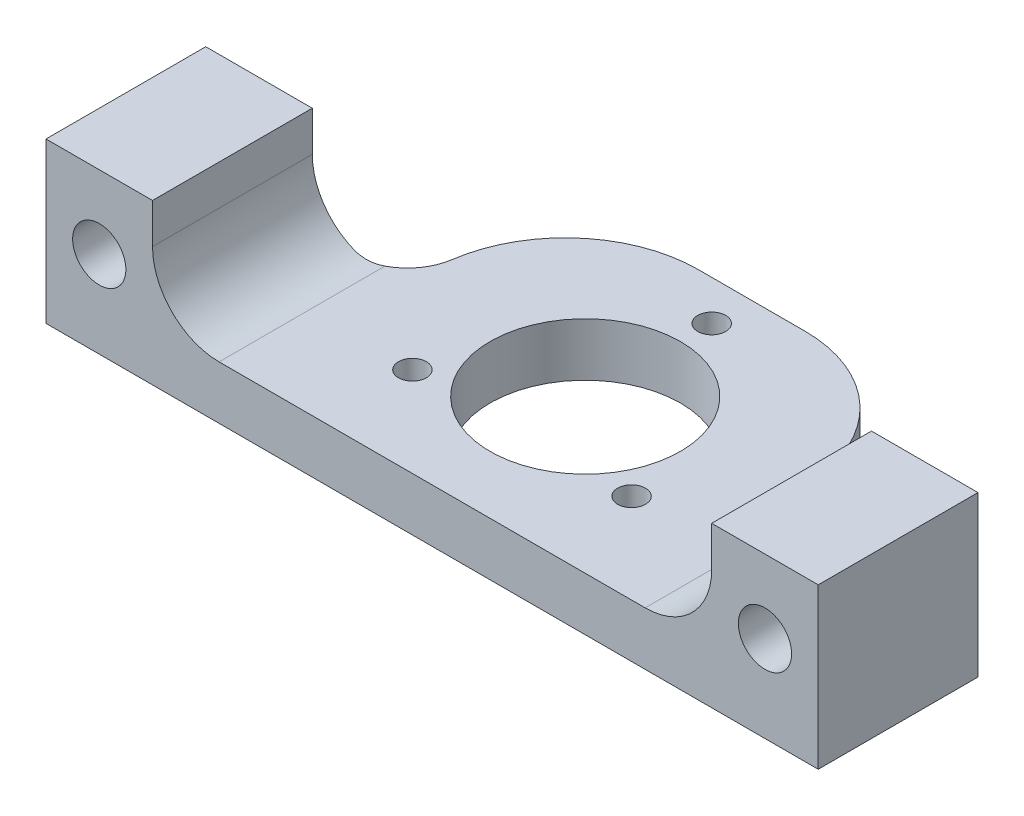
SolidWorks part; units mm, degrees
ref_plane "Front Plane" through (0, 0, 0) normal (0, 0, 1) x (1, 0, 0)
ref_plane "Top Plane" through (0, 0, 0) normal (0, 1, 0) x (1, 0, 0)
ref_plane "Right Plane" through (0, 0, 0) normal (1, 0, 0) x (0, 0, -1)
sketch "Sketch1" plane through (0, 0, 0) normal (0, 0, 1) x (1, 0, 0)
  line L0 (-25, 0.5) -> (25, 0.5) construction
  line L1 (-29, -6) -> (29, -6)
  line L2 (-29, -6) -> (-29, 6)
  line L3 (-29, 6) -> (29, 6)
  line L4 (29, -6) -> (29, 6)
  line L5 (-29, -6) -> (29, 6) construction
  line L6 (-29, 6) -> (29, -6) construction
  circle A0 centre (-25, 0.5) radius 2
  circle A1 centre (25, 0.5) radius 2
  point P0 (0, 0)
  point P11 (0, 0)
  point P13 (0, 0.5)
  dimension "D3" = 4
  dimension "D4" = 4
  dimension "D1" = 58
  dimension "D2" = 12
  dimension "D5" = 50
  dimension "D6" = 6.5
extrude "Main" add sketch "Sketch1" along normal blind 24
sketch "Sketch3" plane through (0, 0, 24) normal (0, 0, 1) x (1, 0, 0)
  line L0 (29, 6) -> (-29, 6) construction
  line L1 (-21, 6) -> (21, 6)
  line L2 (-21, 6) -> (-21, -2)
  line L3 (-21, -2) -> (21, -2)
  line L4 (21, 6) -> (21, -2)
  line L5 (-29, 6) -> (-29, -6) construction
  line L6 (29, -6) -> (29, 6) construction
  line L7 (-29, -6) -> (29, -6) construction
  dimension "D1" = 8
  dimension "D2" = 8
  dimension "D3" = 4
extrude "CoderHole" cut sketch "Sketch3" against normal through all
sketch "Sketch4" plane through (0, -6, 0) normal (0, -1, 0) x (-1, 0, 0)
  line L0 (29, -24) -> (29, 0) construction
  line L1 (29, -12) -> (14, -12)
  line L2 (29, -12) -> (29, 0)
  line L3 (29, 0) -> (14, 0)
  line L4 (14, -12) -> (14, 0)
  line L5 (29, 0) -> (-29, 0) construction
  line L6 (-29, -24) -> (-29, 0) construction
  line L7 (-29, -12) -> (-14, -12)
  line L8 (-29, -12) -> (-29, 0)
  line L9 (-29, 0) -> (-14, 0)
  line L10 (-14, -12) -> (-14, 0)
  dimension "D1" = 28
  dimension "D2" = 12
extrude "Cut-Extrude3" cut sketch "Sketch4" against normal through all
sketch "Sketch5" plane through (0, -6, 0) normal (0, -1, 0) x (-1, 0, 0)
  line L0 (8.2272, -17.25) -> (-8.2272, -17.25) construction
  line L1 (-8.2272, -17.25) -> (0, -3) construction
  line L2 (0, -3) -> (8.2272, -17.25) construction
  line L4 (14, -12) -> (29, -12) construction
  circle A0 centre (0, -12.5) radius 9.5 construction
  circle A1 centre (8.2272, -17.25) radius 1.05
  circle A2 centre (-8.2272, -17.25) radius 1.05
  circle A3 centre (0, -3) radius 1.05
  circle A4 centre (0, -12.5) radius 7.15
  dimension "D1" = 19
  dimension "D2" = 2.1
  dimension "D4" = 14.3
  dimension "D3" = 9
extrude "MainAndFixHole" cut sketch "Sketch5" against normal through all
fillet "Fillet1" radius 10 2 edges at (14, -4, 0) (-14, -4, 0)
sketch "Sketch6" plane through (0, -6, 0) normal (0, -1, 0) x (-1, 0, 0)
  circle A0 centre (8.2272, -17.25) radius 2.2
  circle A1 centre (-8.2272, -17.25) radius 2.2
  circle A2 centre (0, -3) radius 2.2
  dimension "D1" = 4.4
extrude "FixHole2" cut sketch "Sketch6" against normal blind 1.5
fillet "Fillet3" radius 5 2 edges at (-21, -2, 18) (21, -2, 18)
fillet "Fillet4" radius 4 2 edges at (14, -4, 12) (-14, -4, 12)
